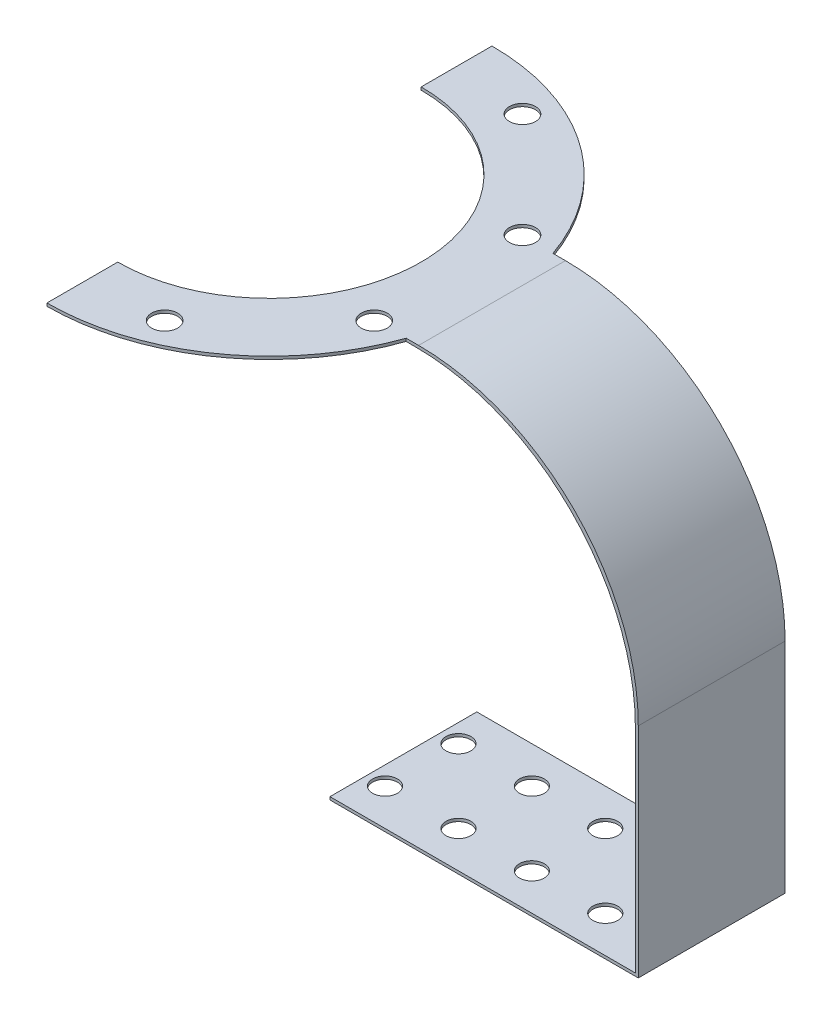
SolidWorks part; units mm, degrees
material "Copper"
ref_plane "Front Plane" through (0, 0, 0) normal (0, 0, 1) x (1, 0, 0)
ref_plane "Top Plane" through (0, 0, 0) normal (0, 1, 0) x (1, 0, 0)
ref_plane "Right Plane" through (0, 0, 0) normal (1, 0, 0) x (0, 0, -1)
sketch "Sketch1" plane through (0, 0, 0) normal (0, 0, 1) x (1, 0, 0)
  line L2 (-53.34, 0.5) -> (-53.34, 0)
  line L4 (-53.34, 0.5) -> (-0.5, 0.5)
  line L5 (-0.5, 0.5) -> (-0.5, 0)
  line L6 (-0.5, 0) -> (-53.34, 0)
  line L7 (0, 0) -> (0, 75.78)
  line L10 (-76.5098, 75.28) -> (-76.5098, 75.78)
  line L11 (-76.5098, 75.78) -> (0, 75.78)
  line L13 (-0.5, 0.5) -> (-0.5, 75.28)
  line L14 (-76.5098, 75.28) -> (-0.5, 75.28)
  line L16 (0, 0) -> (-0.5, 0)
  point P0 (-77.3542, 74.78)
  dimension "D1" = 0.5
  dimension "D2" = 0.5
  dimension "D3" = 0.5
  dimension "D4" = 52.84
  dimension "D5" = 76.5098
  dimension "D6" = 74.78
extrude "Boss-Extrude1" add sketch "Sketch1" along normal blind 25.4
sketch "Sketch2" plane through (0, 75.78, 0) normal (0, 1, 0) x (1, 0, 0)
  line L0 (-76.5098, -25.4) -> (-76.5098, 0) construction
  line L1 (-76.5098, -12.7) -> (-63.6899, 18.25) construction
  line L2 (-76.5098, 25.8) -> (-76.5098, -12.7)
  line L3 (-76.5098, -12.7) -> (-76.5098, -51.2)
  circle A0 centre (-76.5098, -12.7) radius 38.5
  circle A1 centre (-63.6899, 18.25) radius 2.25
  circle A2 centre (-76.5098, -12.7) radius 26.25
  circle A3 centre (-45.5598, 0.1199) radius 2.25
  circle A4 centre (-76.5098, -12.7) radius 38.5
  circle A5 centre (-45.5598, -25.5199) radius 2.25
  circle A6 centre (-76.5098, -12.7) radius 38.5
  circle A7 centre (-63.6899, -43.65) radius 2.25
  circle A8 centre (-76.5098, -12.7) radius 38.5
  circle A9 centre (-89.3297, -43.65) radius 2.25 [skipped]
  circle A10 centre (-76.5098, -12.7) radius 38.5 [skipped]
  circle A11 centre (-107.4598, -25.5199) radius 2.25 [skipped]
  circle A12 centre (-76.5098, -12.7) radius 38.5 [skipped]
  circle A13 centre (-107.4598, 0.1199) radius 2.25 [skipped]
  circle A14 centre (-76.5098, -12.7) radius 38.5 [skipped]
  circle A15 centre (-89.3297, 18.25) radius 2.25 [skipped]
  circle A16 centre (-76.5098, -12.7) radius 38.5 [skipped]
  point P33 (-76.5098, -12.7)
  line M3 (0, 0) -> (-76.5098, 0)
  line M4 (-76.5098, 0) -> (-76.5098, -25.4)
  line M5 (-76.5098, -25.4) -> (0, -25.4)
  dimension "D1" = 77
  dimension "D2" = 52.5
  dimension "D5" = 4.5
  dimension "D3" = 33.5
  dimension "D4" = 22.5
  dimension "D6" = 8
sketch "Sketch3" plane through (0, 0, 0) normal (0, -1, 0) x (-1, 0, 0)
  line L0 (53.34, -25.4) -> (53.34, 0) construction
  line L1 (0, -25.4) -> (53.34, -25.4) construction
  line L2 (37.46, -6.35) -> (50.16, -6.35) construction
  line L3 (50.16, -6.35) -> (50.16, -19.05) construction
  circle A0 centre (50.16, -19.05) radius 2.1526
  circle A1 centre (37.46, -19.05) radius 2.1526
  circle A2 centre (24.76, -19.05) radius 2.1526
  circle A3 centre (12.06, -19.05) radius 2.1526
  circle A4 centre (37.46, -6.35) radius 2.1527
  circle A5 centre (24.76, -6.35) radius 2.1527
  circle A6 centre (12.06, -6.35) radius 2.1526
  circle A7 centre (50.16, -6.35) radius 2.1527
  dimension "D3" = 4.3053
  dimension "D1" = 3.18
  dimension "D2" = 6.35
  dimension "D6" = 12.7
  dimension "D7" = 12.7
  dimension "D4" = 4
  dimension "D5" = 2
extrude "Cut-Extrude1" cut sketch "Sketch3" against normal up to surface (0.5 mm away) up to face at (-26.92, 0.5, 12.7)
extrude "Boss-Extrude2" add sketch "Sketch2" against normal up to surface (0.5 mm away) contours A5 A2 A3 A0 A7 A1 M5 M3 | A5 A2 L3 A0 A7 M5 | A5 A0 A3 A2 M5 M3 region at (-59.4304, 75.78, -13.1904) region at (-45.0173, 75.78, 12.7) region at (-59.4304, 75.78, 38.5904) up to face at (-38.5049, 75.28, 12.7)
extrude "Cut-Extrude2" cut sketch "Sketch2<3>" along direction (0, 1, 0) on the side against the normal up to surface (0.5 mm away) contours A5 M5 | A3 M3 | L1 A2 M4 M5 M3 | L1 M4 M3 region at (-74.7563, 75.78, 4.2333) region at (-63.2997, 75.78, 13.1664) region at (-45.5598, 75.78, 0.9001) region at (-45.5598, 75.78, 24.4999) up to face at (-52.9614, 75.28, 12.7)
sketch "Sketch2<3>" plane through (0, 75.78, 0) normal (0, 1, 0) x (1, 0, 0) same geometry as "Sketch2"
fillet "Fillet2" radius 38 2 edges at (-0.5, 75.28, 12.7) (0, 75.78, 12.7)
